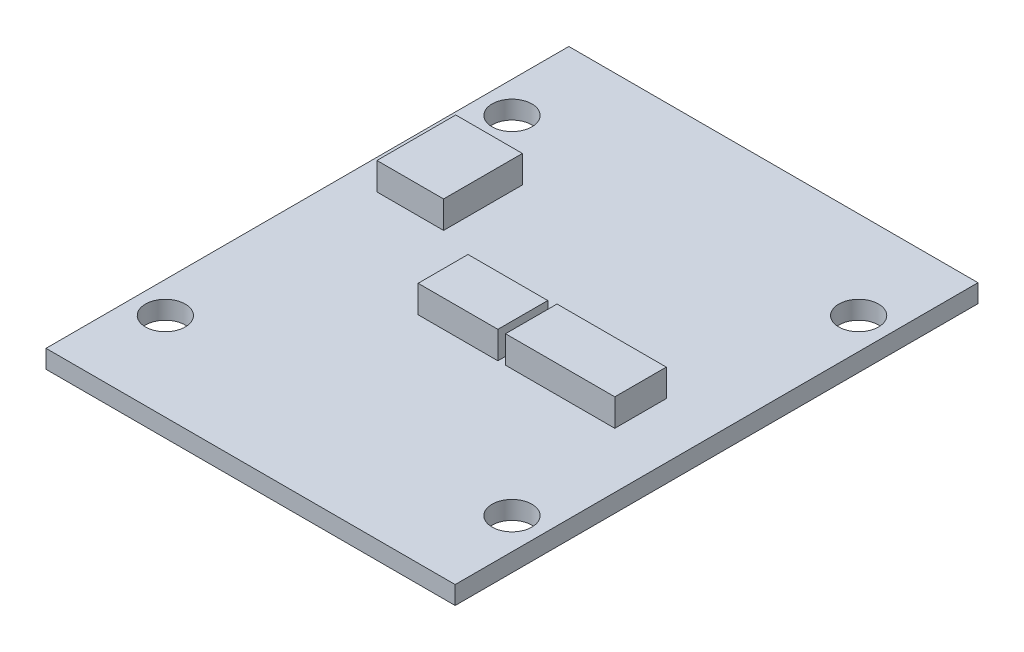
SolidWorks part; units mm, degrees
ref_plane "Front Plane" through (0, 0, 0) normal (0, 0, 1) x (1, 0, 0)
ref_plane "Top Plane" through (0, 0, 0) normal (0, 1, 0) x (1, 0, 0)
ref_plane "Right Plane" through (0, 0, 0) normal (1, 0, 0) x (0, 0, -1)
sketch "Sketch1" plane through (0, 0, 0) normal (0, 1, 0) x (1, 0, 0)
  line L0 (0, 18) -> (0, -18) construction
  line L1 (-18, 23) -> (18, 23)
  line L2 (-18, 23) -> (-18, -23)
  line L3 (-18, -23) -> (18, -23)
  line L4 (18, 23) -> (18, -23)
  line L5 (-18, 23) -> (18, -23) construction
  line L6 (-18, -23) -> (18, 23) construction
  line L7 (18, -18) -> (-18, -18)
  line L8 (18, -18) -> (18, 18)
  line L9 (18, 18) -> (-18, 18)
  line L10 (-18, -18) -> (-18, 18)
  line L11 (18, -18) -> (-18, 18) construction
  line L12 (18, 18) -> (-18, -18) construction
  line L13 (-18, 0) -> (18, 0) construction
  circle A0 centre (-15.25, 15.25) radius 1.75
  circle A1 centre (15.25, 15.25) radius 1.75
  circle A2 centre (-15.25, -15.25) radius 1.75
  circle A3 centre (15.25, -15.25) radius 1.75
  point P0 (0, 0)
  point P6 (0, 0)
  dimension "D3" = 3.5
  dimension "D1" = 46
  dimension "D2" = 36
  dimension "D4" = 30.5
extrude "PCB" add sketch "Sketch1" along normal blind 1.6 contours L9 L4 L1 L2 | L4 L9 L2 L7 A3 A1 A0 A2 | L4 L7 L2 L3 region at (0, 0, -20.5) region at (0, 0, 0) region at (0, 0, 20.5)
sketch "Sketch2" plane through (0, 1.6, 0) normal (0, 1, 0) x (1, 0, 0)
  line L1 (13.118, 0.4566) -> (3.5041, 0.4566)
  line L2 (13.118, 0.4566) -> (13.118, -4.0741)
  line L3 (13.118, -4.0741) -> (3.5041, -4.0741)
  line L4 (3.5041, 0.4566) -> (3.5041, -4.0741)
  line L5 (2.8313, 0.3154) -> (-4.1847, 0.3154)
  line L6 (2.8313, 0.3154) -> (2.8313, -4.0741)
  line L7 (2.8313, -4.0741) -> (-4.1847, -4.0741)
  line L8 (-4.1847, 0.3154) -> (-4.1847, -4.0741)
  line L9 (-15.3548, 10.4054) -> (-9.4909, 10.4054)
  line L10 (-15.3548, 10.4054) -> (-15.3548, 3.472)
  line L11 (-15.3548, 3.472) -> (-9.4909, 3.472)
  line L12 (-9.4909, 10.4054) -> (-9.4909, 3.472)
  point P12 (-9.4909, 3.472)
  point P13 (-15.3548, 10.4054)
  point P14 (-4.1847, 0.3154)
  point P15 (2.8313, -4.0741)
  point P16 (3.5041, -4.0741)
  point P17 (13.118, 0.4566)
extrude "Components" add sketch "Sketch2" along normal offset from surface (2.4 mm away) 4 contours L12 L9 L10 L11 | L5 L8 L7 L6 | L1 L4 L3 L2 region at (8.311, 1.6, 1.8087) region at (-0.6767, 1.6, 1.8793) region at (-12.4229, 1.6, -6.9387) up to face at (0, 0, 0)
